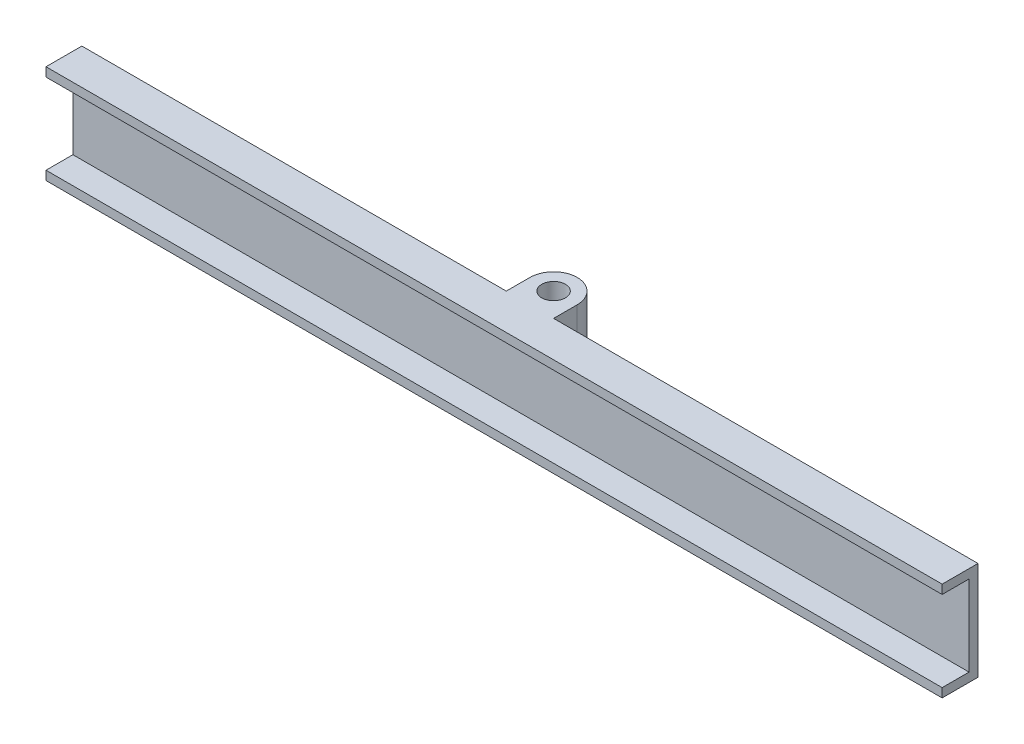
SolidWorks part; units mm, degrees
material "PLA"
ref_plane "Front Plane" through (0, 0, 0) normal (1, 0, 0) x (0, 1, 0)
ref_plane "Top Plane" through (0, 0, 0) normal (0, 0, 1) x (0, 1, 0)
ref_plane "Right Plane" through (0, 0, 0) normal (0, 1, 0) x (-1, 0, 0)
sketch "Sketch1" plane through (0, 0, 0) normal (1, 0, 0) x (0, 1, 0)
  line L16 (0, 7.5) -> (-2.5, 7.5)
  line L17 (0, 0) -> (22.5, 0)
  line L18 (0, 0) -> (0, 7.5)
  line L19 (0, 7.5) -> (22.5, 7.5) construction
  line L20 (22.5, 0) -> (22.5, 7.5)
  line L21 (-2.5, 7.5) -> (-2.5, -2.5)
  line L22 (-2.5, -2.5) -> (25, -2.5)
  line L23 (25, -2.5) -> (25, 7.5)
  line L24 (22.5, 7.5) -> (25, 7.5)
  dimension "D1" = 7.5
  dimension "D2" = 22.5
  dimension "D3" = 2.5
  dimension "D4" = 2.5
extrude "Boss-Extrude1" add sketch "Sketch1" along normal blind 250
sketch "Sketch3" plane through (0, -2.5, 0) normal (0, -1, 0) x (1, 0, 0)
  line L0 (118.4, -2.5) -> (131.6, -2.5)
  line L1 (250, -2.5) -> (0, -2.5) construction
  line L2 (131.6, -2.5) -> (131.6, -9.1)
  line L3 (118.4, -2.5) -> (118.4, -9.1)
  line L4 (0, 7.5) -> (0, -2.5) construction
  arc A0 (118.4, -9.1) -> (131.6, -9.1) centre (125, -9.1) ccw
  circle A1 centre (125, -9.1) radius 3.3
  point P5 (125, -2.5)
  dimension "D1" = 6.6
  dimension "D2" = 6.6
  dimension "D3" = 6.6
  dimension "D4" = 125
extrude "Boss-Extrude2" add sketch "Sketch3" against normal up to surface (27.5 mm away) up to face at (125, 25, 2.5)
equation "\"D1@Sketch1\"=\"ball_diameter\" * 0.25"
equation "\"D2@Sketch1\"=\"ball_diameter\" * 0.75"
equation "\"D3@Sketch1\"=\"wall_thickness\""
equation "\"D4@Sketch1\"=\"wall_thickness\""
equation "\"D1@Boss-Extrude1\"=\"track_length\""
equation "\"D2@Sketch3\"= \"axle\""
equation "\"ball_diameter\"= 3cm"
equation "\"wall_thickness\" = 0.25cm"
equation "\"track_length\" = 25cm"
equation "\"axle\" = 0.66cm"
equation "\"D1@Sketch3\"=\"axle\" "
equation "\"D3@Sketch3\"=\"axle\" * 1"
equation "\"D4@Sketch3\"=\"track_length\" / 2"
